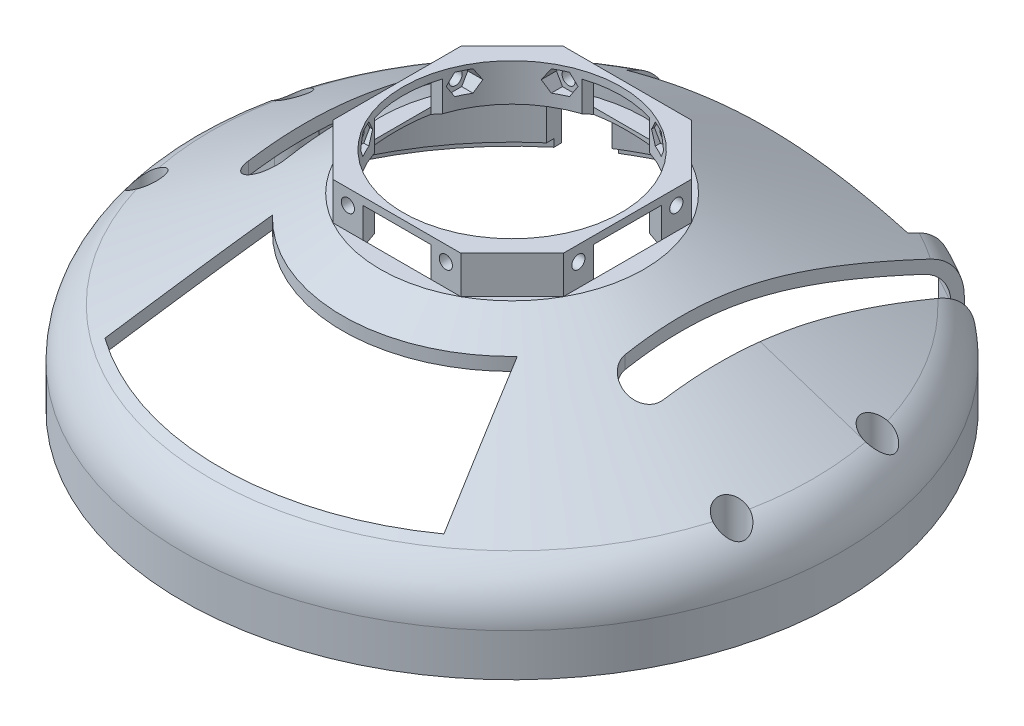
SolidWorks part; units mm, degrees
ref_plane "Front Plane" through (0, 0, 0) normal (0, 0, 1) x (1, 0, 0)
ref_plane "Top Plane" through (0, 0, 0) normal (0, 1, 0) x (1, 0, 0)
ref_plane "Right Plane" through (0, 0, 0) normal (1, 0, 0) x (0, 0, -1)
sketch "Sketch1" plane through (0, 0, 0) normal (0, 0, 1) x (1, 0, 0)
  line L0 (0, 0) -> (-87.5, 0)
  line L1 (-87.5, 0) -> (-87.5, 11.2952)
  line L2 (-79.9421, 24.3188) -> (-35, 50)
  line L3 (-35, 50) -> (0, 50)
  line L4 (0, 50) -> (0, 0)
  arc A0 (-87.5, 11.2952) -> (-79.9421, 24.3188) centre (-72.5, 11.2952) cw
  point P8 (-87.5, 20)
  dimension "D5" = 15
  dimension "D1" = 87.5
  dimension "D2" = 50
  dimension "D3" = 20
  dimension "D4" = 35
revolve "Revolve1" add sketch "Sketch1" angle 360 about L4
shell "Shell2" thickness 3 removed face at (-87.5, 0, 0) removed face at (-35, 50, 0)
sketch "Sketch4" plane through (0, 0, 0) normal (0, 1, 0) x (1, 0, 0)
  line L1 (-37.5, 107.5) -> (37.5, 107.5)
  line L2 (-37.5, 107.5) -> (-37.5, 67.5)
  line L3 (-37.5, 67.5) -> (37.5, 67.5)
  line L4 (37.5, 107.5) -> (37.5, 67.5)
  line L5 (-37.5, 107.5) -> (37.5, 67.5) construction
  line L6 (-37.5, 67.5) -> (37.5, 107.5) construction
  circle A0 centre (0, 0) radius 87.5 construction
  point P0 (0, 87.5)
  dimension "D1" = 75
  dimension "D2" = 40
extrude "Cut-Extrude2" cut sketch "Sketch4" along normal through all
sketch "Sketch5" plane through (0, 0, 0) normal (0, -1, 0) x (1, 0, 0)
  circle A0 centre (0, 0) radius 86
  arc A1 (37.5, -79.0569) -> (-37.5, -79.0569) centre (0, 0) ccw construction
  dimension "D1" = 1.5
extrude "Cut-Extrude3" cut sketch "Sketch5" against normal blind 2
sketch "Sketch7" plane through (0, 2, 0) normal (0, -1, 0) x (1, 0, 0)
  line L0 (-77.6237, 19.3538) -> (0, 0) construction
  line L1 (0, 0) -> (-84.5, 0) construction
  line L2 (-75.0676, 23.651) -> (-80.1746, 26.6888)
  line L3 (-80.1746, 26.6888) -> (-83.3195, 14.0749) construction
  line L4 (-83.3195, 14.0749) -> (-77.3842, 14.3595)
  line L5 (-81.7471, 20.3818) -> (-77.6237, 19.3538) construction
  circle A0 centre (-77.6237, 19.3538) radius 1.75
  arc A1 (-77.3842, 14.3595) -> (-75.0676, 23.651) centre (-77.6237, 19.3538) ccw
  arc A3 (-80.1746, 26.6888) -> (-83.3195, 14.0749) centre (0, 0) ccw
  arc A4 (37.5, -75.7232) -> (-37.5, -75.7232) centre (0, 0) ccw construction
  dimension "D2" = 3.5
  dimension "D3" = 10
  dimension "D1" = 80
  dimension "D4" = 14
  dimension "D5" = 13
extrude "Boss-Extrude1" add sketch "Sketch7" against normal up to next
sketch "Sketch8" plane through (0, 50, 0) normal (0, 1, 0) x (1, 0, 0)
  circle A0 centre (-77.6237, -19.3538) radius 4
  circle A1 centre (-77.6237, -19.3538) radius 1.75 construction
  circle A2 centre (-77.6237, -19.3538) radius 1.75 construction
  dimension "D2" = 8
extrude "Cut-Extrude4" cut sketch "Sketch8" against normal blind 43
mirror "Mirror1" about plane through (0, 0, 0) normal (1, 0, 0) of "Cut-Extrude4", "Boss-Extrude1" second plane through (0, 0, 0) second plane normal (0, 0, 1)
sketch "Sketch9" plane through (0, 0, 0) normal (0, 1, 0) x (1, 0, 0)
  line L0 (-50, 82.5) -> (-50, -15) construction
  line L1 (-45, 82.5) -> (-45, -15)
  line L2 (-55, 82.5) -> (-55, -15)
  line L3 (50, -15) -> (50, 82.5) construction
  line L4 (45, -15) -> (45, 82.5)
  line L5 (55, -15) -> (55, 82.5)
  line L6 (-50, 82.5) -> (50, 82.5) construction
  line L7 (-50, -15) -> (50, -15) construction
  line L8 (0, 0) -> (0, -15) construction
  line L9 (37.5, 67.5) -> (-37.5, 67.5) construction
  arc A0 (-45, 82.5) -> (-55, 82.5) centre (-50, 82.5) ccw
  arc A1 (-55, -15) -> (-45, -15) centre (-50, -15) ccw
  arc A2 (45, -15) -> (55, -15) centre (50, -15) ccw
  arc A3 (55, 82.5) -> (45, 82.5) centre (50, 82.5) ccw
  point P2 (-50, 33.75)
  point P7 (50, 33.75)
  dimension "D1" = 100
  dimension "D2" = 15
  dimension "D3" = 10
  dimension "D4" = 15
extrude "Cut-Extrude5" cut sketch "Sketch9" along normal through all
sketch "Sketch10" plane through (0, 0, 0) normal (0, 1, 0) x (1, 0, 0)
  line L0 (-32.5, -31.1247) -> (-45, -63.0971)
  line L1 (-45, -63.0971) -> (45, -63.0971) construction
  line L2 (45, -63.0971) -> (32.5, -31.1247)
  line L3 (32.5, -31.1247) -> (-32.5, -31.1247) construction
  arc A0 (-32.5, -31.1247) -> (32.5, -31.1247) centre (0, 0) ccw
  arc A1 (-45, -63.0971) -> (45, -63.0971) centre (0, 0) ccw
  arc A2 (-55, 68.0533) -> (55, 68.0533) centre (0, 0) ccw construction
  circle A4 centre (0, 0) radius 35 construction
  dimension "D1" = 10
  dimension "D2" = 10
  dimension "D3" = 90
  dimension "D4" = 65
extrude "Cut-Extrude6" cut sketch "Sketch10" along normal through all
sketch "Sketch11" plane through (0, 50, 0) normal (0, 1, 0) x (1, 0, 0)
  line L1 (-17, 30.5941) -> (-30.5941, 17)
  line L2 (-30.5941, 17) -> (-30.5941, -17)
  line L3 (-30.5941, -17) -> (-17, -30.5941)
  line L4 (-17, -30.5941) -> (17, -30.5941)
  line L5 (17, -30.5941) -> (30.5941, -17)
  line L6 (30.5941, -17) -> (30.5941, 17)
  line L7 (30.5941, 17) -> (17, 30.5941)
  line L8 (17, 30.5941) -> (-17, 30.5941)
  circle A0 centre (0, 0) radius 28.9533 construction
  circle A3 centre (0, 0) radius 28.9533
  circle A4 centre (0, 0) radius 35 construction
  dimension "D1" = 34
extrude "Boss-Extrude2" add sketch "Sketch11" along normal blind 10
sketch "Sketch13" plane through (0, 0, 30.5941) normal (0, 0, 1) x (1, 0, 0)
  line L0 (0, 58) -> (0, 60) construction
  line L1 (-9, 58) -> (9, 58)
  line L2 (-9, 58) -> (-9, 48)
  line L3 (-9, 48) -> (9, 48)
  line L4 (9, 58) -> (9, 48)
  line L5 (-9, 58) -> (9, 48) construction
  line L6 (-9, 48) -> (9, 58) construction
  line L7 (-17, 60) -> (17, 60) construction
  line L8 (-13, 56) -> (13, 56) construction
  line L9 (0, 56) -> (0, 58) construction
  circle A0 centre (-13, 56) radius 1.75
  circle A1 centre (13, 56) radius 1.75
  point P0 (0, 53)
  dimension "D2" = 3.5
  dimension "D1" = 26
  dimension "D3" = 4
  dimension "D4" = 2
  dimension "D5" = 18
  dimension "D6" = 10
extrude "Cut-Extrude7" cut sketch "Sketch13" against normal blind 10
sketch "Sketch14" plane through (0, 0, 0) normal (0, 0, 1) x (1, 0, 0)
  line L1 (-9.7668, 56) -> (-11.3834, 58.8)
  line L2 (-11.3834, 58.8) -> (-14.6166, 58.8)
  line L3 (-14.6166, 58.8) -> (-16.2332, 56)
  line L4 (-16.2332, 56) -> (-14.6166, 53.2)
  line L5 (-14.6166, 53.2) -> (-11.3834, 53.2)
  line L6 (-11.3834, 53.2) -> (-9.7668, 56)
  line L7 (16.2332, 56) -> (14.6166, 58.8)
  line L8 (14.6166, 58.8) -> (11.3834, 58.8)
  line L9 (11.3834, 58.8) -> (9.7668, 56)
  line L10 (9.7668, 56) -> (11.3834, 53.2)
  line L11 (11.3834, 53.2) -> (14.6166, 53.2)
  line L12 (14.6166, 53.2) -> (16.2332, 56)
  circle A0 centre (-13, 56) radius 2.8 construction
  circle A1 centre (13, 56) radius 2.8 construction
  dimension "D1" = 5.6
extrude "Cut-Extrude8" cut sketch "Sketch14" along normal blind 28
pattern_circular "CirPattern1" count 4 over 360 about axis through (0, 60, 0) along (0, 1, 0) of "Cut-Extrude7", "Cut-Extrude8"
